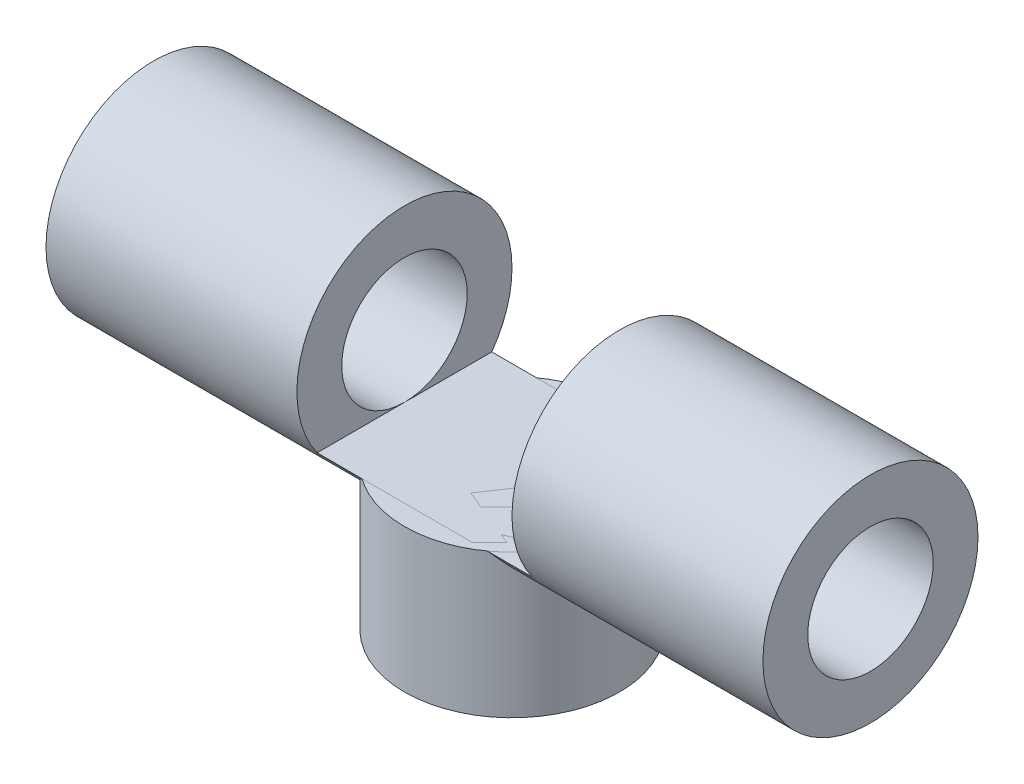
SolidWorks part; units mm, degrees
ref_plane "Plano frontal" through (0, 0, 0) normal (0, 0, 1) x (1, 0, 0)
ref_plane "Plano superior" through (0, 0, 0) normal (0, 1, 0) x (1, 0, 0)
ref_plane "Plano direito" through (0, 0, 0) normal (1, 0, 0) x (0, 0, -1)
sketch "Esboço3" plane through (0, 0, 0) normal (0, 1, 0) x (1, 0, 0)
  circle A1 centre (0, 0) radius 15
  dimension "D2" = 30
extrude "Ressalto-extrusão2" add sketch "Esboço3" along normal blind 20
sketch "Esboço5" plane through (0, 0, 0) normal (1, 0, 0) x (0, 0, -1)
  line L0 (0, 20) -> (0, 28.75) construction
  line L1 (15, 20) -> (-15, 20) construction
  circle A0 centre (0, 28.75) radius 15
  circle A1 centre (0, 28.75) radius 8.75
  dimension "D2" = 17.5
  dimension "D3" = 30
extrude "Ressalto-extrusão3" add sketch "Esboço5" along normal blind 50 and the other way blind 50 separate body
sketch "Esboço6" plane through (0, 0, 0) normal (0, 1, 0) x (1, 0, 0)
  line L0 (50, 15) -> (-50, 15) construction
  line L1 (-15, 15) -> (15, 15)
  line L2 (-15, 15) -> (-15, -15)
  line L3 (-15, -15) -> (15, -15)
  line L4 (15, 15) -> (15, -15)
  line L5 (-15, 15) -> (15, -15) construction
  line L6 (-15, -15) -> (15, 15) construction
  point P0 (0, 0)
  dimension "D2" = 30
extrude "Corte-extrusão2" cut sketch "Esboço6" along normal through all from surface starting at face at (0, 20, 15)
